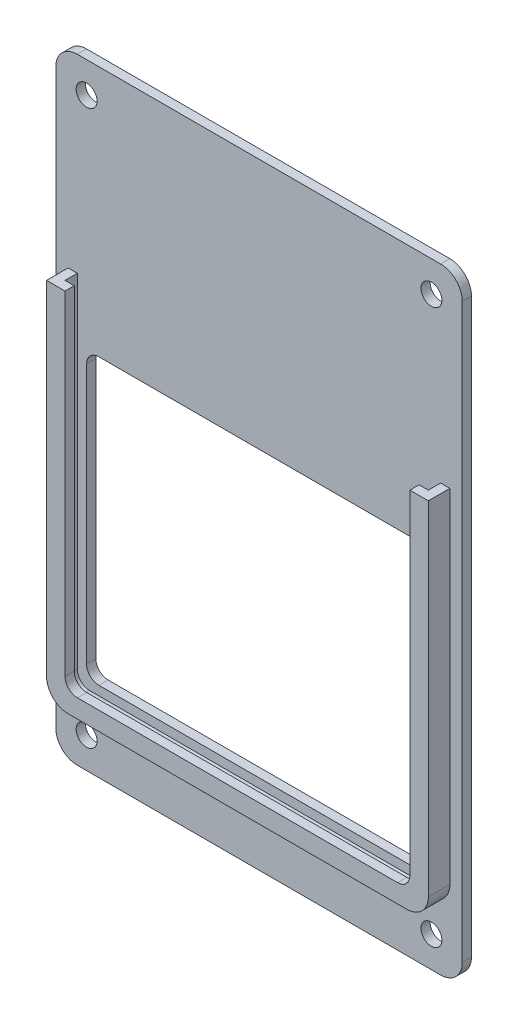
SolidWorks part; units mm, degrees
material "ABS"
ref_plane "Спереди" through (0, 0, 0) normal (0, 0, 1) x (1, 0, 0)
ref_plane "Сверху" through (0, 0, 0) normal (0, 1, 0) x (1, 0, 0)
ref_plane "Справа" through (0, 0, 0) normal (1, 0, 0) x (0, 0, -1)
sketch "Эскиз1" plane through (0, 0, 0) normal (0, 0, 1) x (1, 0, 0)
  line L1 (-33, -50) -> (33, -50)
  line L2 (-33, -50) -> (-33, 50)
  line L3 (-33, 50) -> (33, 50)
  line L4 (33, -50) -> (33, 50)
  line L5 (-33, -50) -> (33, 50) construction
  line L6 (-33, 50) -> (33, -50) construction
  point P0 (0, 0)
  dimension "D1" = 100
  dimension "D2" = 66
extrude "Бобышка-Вытянуть1" add sketch "Эскиз1" along normal blind 1.5 contours L2 L3 L4 L1
fillet "Скругление1" radius 3.5 4 edges at (-33, -50, 0.75) (33, -50, 0.75) (33, 50, 0.75) (-33, 50, 0.75)
sketch "Эскиз2" plane through (0, 0, 1.5) normal (0, 0, 1) x (1, 0, 0)
  line L0 (-29.5, -50) -> (29.5, -50) construction
  line L1 (-33, -50) -> (-24, -50)
  line L2 (-33, -50) -> (-33, -41)
  line L3 (-33, -41) -> (-24, -41)
  line L4 (-24, -50) -> (-24, -41)
  line L5 (33, -50) -> (24, -50)
  line L6 (33, -50) -> (33, -41)
  line L7 (33, -41) -> (24, -41)
  line L8 (24, -50) -> (24, -41)
  line L9 (-28, 9.2) -> (28, 9.2)
  line L10 (-28, 9.2) -> (-28, -37)
  line L11 (-28, -37) -> (28, -37)
  line L12 (28, 9.2) -> (28, -37)
  line L13 (-33, -46.5) -> (-33, 46.5) construction
  line L14 (33, -46.5) -> (33, 46.5) construction
  dimension "D1" = 46.2
  dimension "D2" = 5
  dimension "D3" = 5
  dimension "D4" = 13
  dimension "D5" = 9
extrude "Вырез-Вытянуть1" cut sketch "Эскиз2" against normal blind 1.5 contours L12 L9 L10 L3 L4 L11 L8 L7 region at (0, -13.9, 1.5)
fillet "Скругление2" radius 2 4 edges at (-28, -37, 0.75) (28, -37, 0.75) (-28, 9.2, 0.75) (28, 9.2, 0.75)
sketch "Эскиз3" plane through (0, 0, 1.5) normal (0, 0, 1) x (1, 0, 0)
  line L0 (-26, 9.2) -> (26, 9.2) construction
  line L1 (-28, -37) -> (28, -37)
  line L2 (-28, -37) -> (-28, 9.2)
  line L3 (-28, 9.2) -> (28, 9.2)
  line L4 (28, -37) -> (28, 9.2)
  line L5 (-29.5, -38.5) -> (29.5, -38.5)
  line L6 (-29.5, -38.5) -> (-29.5, 19.2)
  line L7 (-29.5, 19.2) -> (29.5, 19.2)
  line L8 (29.5, -38.5) -> (29.5, 19.2)
  line L10 (-26, -37) -> (26, -37) construction
  line L11 (28, 7.2) -> (28, -35) construction
  line L12 (-28, 7.2) -> (-28, -35) construction
  line L14 (-31, 19.2) -> (31, 19.2)
  line L15 (-31, 19.2) -> (-31, -40)
  line L16 (-31, -40) -> (31, -40)
  line L17 (31, 19.2) -> (31, -40)
  dimension "D1" = 1.5
  dimension "D2" = 1.5
  dimension "D3" = 1.5
  dimension "D4" = 10
  dimension "D5" = 1.5
  dimension "D6" = 1.5
  dimension "D7" = 1.5
extrude "Бобышка-Вытянуть2" add sketch "Эскиз3" along normal blind 2 contours L17 L14 L8 L5 L6 L15 L16 region at (0, -39.3572, 1.5)
fillet "Скругление3" radius 2 2 edges at (29.5, -38.5, 2.5) (-29.5, -38.5, 2.5)
sketch "Эскиз4" plane through (0, 0, 3.5) normal (0, 0, 1) x (1, 0, 0)
  line L0 (-28, 7.2) -> (-28, -35) construction
  line L1 (-31, -40) -> (31, -40)
  line L2 (-31, -40) -> (-31, 19.2)
  line L3 (-31, 19.2) -> (31, 19.2)
  line L4 (31, -40) -> (31, 19.2)
  line L5 (-28, 19.2) -> (28, 19.2)
  line L6 (-28, 19.2) -> (-28, -37)
  line L7 (-28, -37) -> (28, -37)
  line L8 (28, 19.2) -> (28, -37)
  line L9 (-26, -37) -> (26, -37) construction
  line L10 (28, 7.2) -> (28, -35) construction
  line M4 (31, -40) -> (31, 19.2)
  line M5 (31, 19.2) -> (29.5, 19.2)
  line M6 (29.5, 19.2) -> (29.5, -36.5)
  arc M7 (29.5, -36.5) -> (27.5, -38.5) centre (27.5, -36.5) cw
  line M8 (27.5, -38.5) -> (-27.5, -38.5)
  arc M9 (-27.5, -38.5) -> (-29.5, -36.5) centre (-27.5, -36.5) cw
  line M10 (-29.5, -36.5) -> (-29.5, 19.2)
  line M11 (-29.5, 19.2) -> (-31, 19.2)
  line M12 (-31, 19.2) -> (-31, -40)
  line M13 (-31, -40) -> (31, -40)
extrude "Бобышка-Вытянуть3" add sketch "Эскиз4" along normal blind 1.5 contours M13 M4 M5 M6 M7 M8 M9 M10 M11 M12 | L3 L8 L7 L6 M10 M9 M8 M7 M6 region at (-30.1428, -10.4, 3.5) region at (-28.75, 18.3748, 3.5)
fillet "Скругление4" radius 2 2 edges at (-28, -37, 4.25) (28, -37, 4.25)
fillet "Скругление5" radius 3.5 2 edges at (-31, -40, 3.25) (31, -40, 3.25)
sketch "Эскиз5" plane through (0, 0, 0) normal (0, 0, -1) x (-1, 0, 0)
  line L1 (-24, -38.5) -> (24, -38.5)
  line L2 (-24, -38.5) -> (-24, -48.5)
  line L3 (-24, -48.5) -> (24, -48.5)
  line L4 (24, -38.5) -> (24, -48.5)
  line L5 (-31.5, 48.5) -> (31.5, 48.5)
  line L6 (-31.5, 48.5) -> (-31.5, 10.7)
  line L7 (-31.5, 10.7) -> (31.5, 10.7)
  line L8 (31.5, 48.5) -> (31.5, 10.7)
  line L9 (31.5, 48.5) -> (24, 48.5)
  line L10 (31.5, 48.5) -> (31.5, 41)
  line L11 (31.5, 41) -> (24, 41)
  line L12 (24, 48.5) -> (24, 41)
  line L13 (-31.5, 48.5) -> (-24, 48.5)
  line L14 (-31.5, 48.5) -> (-31.5, 41)
  line L15 (-31.5, 41) -> (-24, 41)
  line L16 (-24, 48.5) -> (-24, 41)
  line L18 (-33, -46.5) -> (-33, 46.5) construction
  line L19 (29.5, 50) -> (-29.5, 50) construction
  line L20 (29.5, -50) -> (-29.5, -50) construction
  dimension "D1" = 7.5
  dimension "D2" = 37.8
  dimension "D3" = 63
  dimension "D4" = 1.5
  dimension "D5" = 1.5
  dimension "D6" = 10
  dimension "D7" = 48
  dimension "D8" = 1.5
  dimension "D9" = 9
extrude "Бобышка-Вытянуть4" add sketch "Эскиз5" along normal blind 1.5 contours L5 L16 L15 L6 L7 L8 L11 L12 | L4 L1 L2 L3 region at (0, -43.5, 0) region at (0, 28.8488, 0)
fillet "Скругление6" radius 1.5 10 edges at (24, 48.5, -0.75) (31.5, 41, -0.75) (31.5, 10.7, -0.75) (-31.5, 10.7, -0.75) (-31.5, 41, -0.75) (-24, 48.5, -0.75) (-24, -48.5, -0.75) (-24, -38.5, -0.75) (24, -38.5, -0.75) (24, -48.5, -0.75)
fillet "Скругление7" radius 4 2 edges at (-24, 41, -0.75) (24, 41, -0.75)
sketch "Эскиз6" plane through (0, 0, 1.5) normal (0, 0, 1) x (1, 0, 0)
  line L1 (-29.5, 50) -> (29.5, 50) construction
  line L2 (-33, -46.5) -> (-33, 46.5) construction
  line L3 (33, -46.5) -> (33, 46.5) construction
  line L4 (-29.5, -50) -> (29.5, -50) construction
  point P0 (-28, 45)
  point P1 (28, 45)
  point P3 (-28, -45)
  point P4 (28, -45)
  dimension "D1" = 5
  dimension "D2" = 5
  dimension "D3" = 5
  dimension "D4" = 5
hole_wizard "Отверстие с зазором M31" positions "Эскиз7" profile "Эскиз8" hole size "M3" standard "DIN" end condition through all
sketch "Эскиз7" plane through (0, 0, 1.5) normal (0, 0, 1) x (1, 0, 0)
  point P0 (-28, 45)
  point P3 (28, 45)
  point P6 (28, -45)
  point P9 (-28, -45)
sketch "Эскиз8" plane through (-28, 45, 1.5) normal (1, 0, 0) x (0, -1, 0)
  line L0 (0, 0) -> (0, 3)
  line L1 (0, 3) -> (1.7, 3)
  line L2 (1.7, 3) -> (1.7, 0)
  line L5 (1.7, 0) -> (0, 0)
  line L11 (0, -6.35) -> (0, 107.95) construction
  dimension "Диаметр сквозного отверстия" = 3.4
  dimension "Глубина сквозного отверстия" = 3
sketch "Эскиз9" plane through (0, 0, -1.5) normal (0, 0, -1) x (-1, 0, 0)
  line L0 (-23, 45) -> (-23, 47)
  line L1 (-22.5, 47.5) -> (22.5, 47.5)
  line L2 (23, 47) -> (23, 45)
  line L3 (28, 40) -> (30, 40)
  line L4 (30.5, 39.5) -> (30.5, 12.2)
  line L5 (30, 11.7) -> (-30, 11.7)
  line L6 (-30.5, 12.2) -> (-30.5, 39.5)
  line L7 (-30, 40) -> (-28, 40)
  line L8 (-22.5, -39.5) -> (22.5, -39.5)
  line L9 (23, -40) -> (23, -47)
  line L10 (22.5, -47.5) -> (-22.5, -47.5)
  line L11 (-23, -47) -> (-23, -40)
  line L12 (-22.5, 48.5) -> (22.5, 48.5) construction
  line L14 (-31.5, 39.5) -> (-31.5, 12.2) construction
  line L15 (-24, -40) -> (-24, -47) construction
  line L16 (24, -40) -> (24, -47) construction
  line L17 (-22.5, -38.5) -> (22.5, -38.5) construction
  line L18 (-22.5, -48.5) -> (22.5, -48.5) construction
  line L19 (31.5, 39.5) -> (31.5, 12.2) construction
  line L20 (30, 41) -> (28, 41) construction
  line L21 (24, 47) -> (24, 45) construction
  line L22 (-30, 41) -> (-28, 41) construction
  line L23 (-24, 47) -> (-24, 45) construction
  line L24 (-30, 10.7) -> (30, 10.7) construction
  arc A0 (22.5, -39.5) -> (23, -40) centre (22.5, -40) cw
  arc A1 (23, -47) -> (22.5, -47.5) centre (22.5, -47) cw
  arc A2 (-22.5, -47.5) -> (-23, -47) centre (-22.5, -47) cw
  arc A3 (-22.5, -39.5) -> (-23, -40) centre (-22.5, -40) ccw
  arc A4 (-30.5, 39.5) -> (-30, 40) centre (-30, 39.5) cw
  arc A5 (-30, 11.7) -> (-30.5, 12.2) centre (-30, 12.2) cw
  arc A6 (30.5, 12.2) -> (30, 11.7) centre (30, 12.2) cw
  arc A7 (30, 40) -> (30.5, 39.5) centre (30, 39.5) cw
  arc A8 (22.5, 47.5) -> (23, 47) centre (22.5, 47) cw
  arc A9 (-23, 47) -> (-22.5, 47.5) centre (-22.5, 47) cw
  arc A10 (23, 45) -> (28, 40) centre (28, 45) ccw
  arc A11 (-23, 45) -> (-28, 40) centre (-28, 45) cw
  dimension "D13" = 0.5
  dimension "D14" = 5
  dimension "D1" = 1
  dimension "D2" = 1
  dimension "D3" = 1
  dimension "D4" = 1
  dimension "D5" = 1
  dimension "D6" = 1
  dimension "D7" = 1
  dimension "D8" = 1
  dimension "D9" = 1
  dimension "D10" = 1
  dimension "D11" = 1
  dimension "D12" = 1
extrude "Вырез-Вытянуть3" cut sketch "Эскиз9" against normal up to surface (1.5 mm away) up to face at (-26.3, 45, 0)
